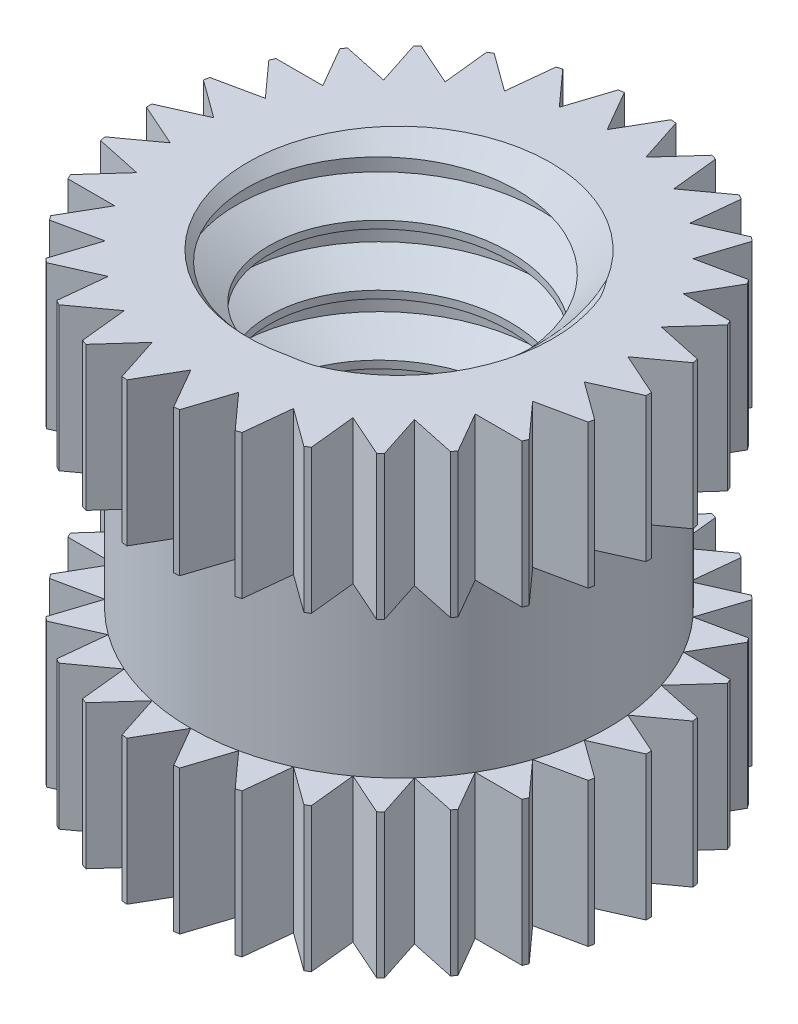
SolidWorks part; units mm, degrees
ref_plane "Plan de face" through (0, 0, 0) normal (0, 0, 1) x (1, 0, 0)
ref_plane "Plan de dessus" through (0, 0, 0) normal (0, 1, 0) x (1, 0, 0)
ref_plane "Plan de droite" through (0, 0, 0) normal (1, 0, 0) x (0, 0, -1)
sketch "Esquisse1" plane through (0, 0, 0) normal (0, 0, 1) x (1, 0, 0)
  line L0 (0.8, 0) -> (0.8, 3)
  line L1 (0.8, 3) -> (1.65, 3)
  line L2 (1.65, 3) -> (1.65, 2.05)
  line L3 (1.65, 2.05) -> (1.375, 2.05)
  line L4 (1.375, 2.05) -> (1.375, 0.95)
  line L5 (1.375, 0.95) -> (1.65, 0.95)
  line L6 (1.65, 0.95) -> (1.65, 0)
  line L7 (1.65, 0) -> (0.8, 0)
  line L8 (0, 0) -> (0, 3) construction
  dimension "D1" = 3
  dimension "D2" = 0.8
  dimension "D3" = 1.375
  dimension "D4" = 1.65
  dimension "D5" = 0.95
  dimension "D6" = 0.95
revolve "Révolution1" add sketch "Esquisse1" angle 360 about L8
sketch "Esquisse2" plane through (0, 3, 0) normal (0, 1, 0) x (1, 0, 0)
  line L0 (-0.25, 1.808) -> (0, 1.375)
  line L1 (0, 1.375) -> (0.25, 1.808)
  line L2 (0.25, 1.808) -> (-0.25, 1.808)
  line L3 (0, 0) -> (0, 2.7648) construction
  circle A0 centre (0, 0) radius 1.375 construction
  point P6 (0, 0)
  point P7 (0, 0)
  dimension "D1" = 60
  dimension "D2" = 60
  dimension "D3" = 0.5
extrude "Enlèv. mat.-Extru.1" cut sketch "Esquisse2" against normal up to surface (3 mm away) up to face at (0, 0, -1.65)
pattern_circular "Répétition circulaire1" count 30 over 360 about axis through (0, 3, 0) along (0, -1, 0) of "Enlèv. mat.-Extru.1"
chamfer "Chanfrein1" distance 0.2 angle 45 2 edges at (0, 0, -0.8) (0, 3, -0.8)
thread "Filetage1" pitch 0.4 method cut profile "Profil de filetage1" start angle 0, offset 1, length 0, pitch 0.4, diameter 1.6
ref_plane "Plan1" through (-0.8, 3.8, 0) normal (0, 0, -1) x (1, 0, 0)
sketch "Profil de filetage1" plane through (-0.8, 3.8, 0) normal (0, 0, -1) x (1, 0, 0)
  line L0 (0, 0) -> (0, 0.4) construction
  line L11 (0, 0) -> (0, 0.35)
  line L12 (0, 0.35) -> (-0.2165, 0.225)
  line L13 (-0.2165, 0.225) -> (-0.2165, 0.125)
  line L15 (-0.2165, 0.125) -> (0, 0)
  line L17 (-0.2165, 0.175) -> (0, 0.175) construction
  point P2 (0, 0)
  dimension "Pitch" = 0.4
  dimension "Profile_Angle" = 60
  dimension "Profile_Land" = 0.1
  dimension "Profile_Height" = 0.2165
